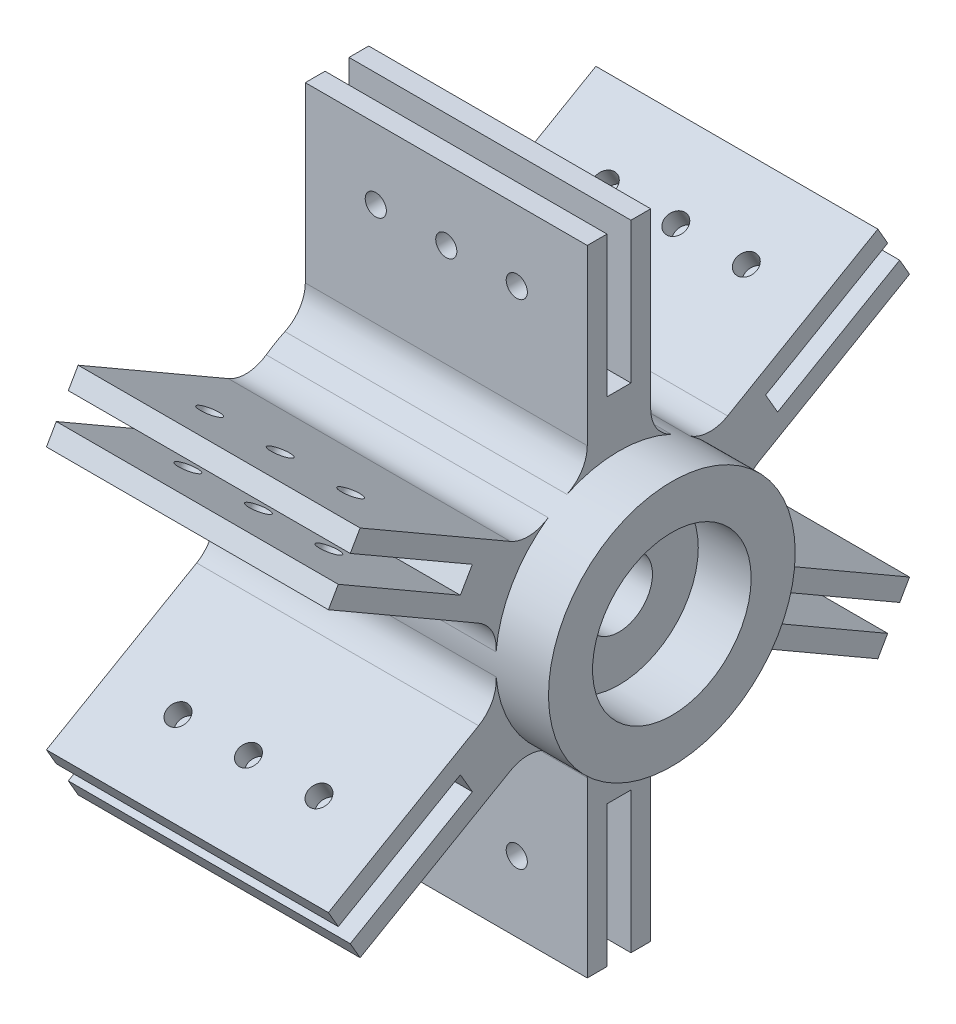
SolidWorks part; units mm, degrees
ref_plane "Front Plane" through (0, 0, 0) normal (0, 0, 1) x (1, 0, 0)
ref_plane "Top Plane" through (0, 0, 0) normal (0, 1, 0) x (1, 0, 0)
ref_plane "Right Plane" through (0, 0, 0) normal (1, 0, 0) x (0, 0, -1)
sketch "Sketch1" plane through (0, 0, 0) normal (1, 0, 0) x (0, 0, -1)
  circle A0 centre (0, 0) radius 17.5
  circle A1 centre (0, 0) radius 4.75
  dimension "D1" = 35
  dimension "D2" = 9.5
extrude "MainBody" add sketch "Sketch1" along normal blind 40
sketch "Sketch2" plane through (40, 0, 0) normal (1, 0, 0) x (0, 0, -1)
  circle A0 centre (0, 0) radius 17.5 construction
  circle A1 centre (0, 0) radius 17.5
  circle A2 centre (0, 0) radius 11.25
  dimension "D1" = 22.5
extrude "BearingHousing" add sketch "Sketch2" along normal blind 7.5
sketch "Sketch3" plane through (0, 0, 0) normal (-1, 0, 0) x (0, 0, 1)
  circle A0 centre (0, 13) radius 1.5
  circle A1 centre (11.2583, 6.5) radius 1.5
  circle A2 centre (11.2583, -6.5) radius 1.5
  circle A3 centre (0, -13) radius 1.5
  circle A4 centre (-11.2583, -6.5) radius 1.5
  circle A5 centre (-11.2583, 6.5) radius 1.5
  point P15 (0, 0)
  dimension "D1" = 3
  dimension "D2" = 13
extrude "MountingHoles" cut sketch "Sketch3" against normal blind 20
sketch "Sketch4" plane through (0, 0, 0) normal (-1, 0, 0) x (0, 0, 1)
  line L0 (0, 0) -> (0, 30) construction
  line L1 (-4.5, 16.9115) -> (-4.5, 45)
  line L2 (-4.5, 45) -> (-1.7, 45)
  line L3 (-1.7, 45) -> (-1.7, 25)
  line L4 (-1.7, 25) -> (1.7, 25)
  line L5 (1.7, 45) -> (1.7, 25)
  line L6 (4.5, 45) -> (1.7, 45)
  line L7 (4.5, 16.9115) -> (4.5, 45)
  circle A0 centre (0, 0) radius 17.5 construction
  arc A1 (4.5, 16.9115) -> (-4.5, 16.9115) centre (0, 0) ccw
  circle A3 centre (0, 0) radius 4.75 construction
  point P9 (0, 45)
  point P11 (0, 25)
  dimension "D1" = 30
  dimension "D2" = 4.5
  dimension "D3" = 45
  dimension "D4" = 1.7
  dimension "D5" = 20
  dimension "D6" = 2.8
extrude "Boss-Extrude3" add sketch "Sketch4" against normal blind 40
sketch "Sketch6" plane through (0, 0, -4.5) normal (0, 0, -1) x (-1, 0, 0)
  line L0 (-40, 45) -> (0, 45) construction
  line L1 (-40, 45) -> (-40, 16.9115) construction
  circle A0 centre (-30, 35) radius 1.5
  circle A1 centre (-20, 35) radius 1.5
  circle A2 centre (-10, 35) radius 1.5
  dimension "D1" = 10
  dimension "D2" = 3
  dimension "D3" = 10
  dimension "D5" = 10
  dimension "D4" = 3
extrude "Cut-Extrude2" cut sketch "Sketch6" against normal blind 10
fillet "Fillet1" radius 5 2 edges at (20, 16.9115, -4.5) (20, 16.9115, 4.5)
pattern_circular "CirPattern1" count 6 over 360 about axis through (40, 0, 0) along (-1, 0, 0) of "Boss-Extrude3", "Cut-Extrude2", "Fillet1" reverse direction yes
